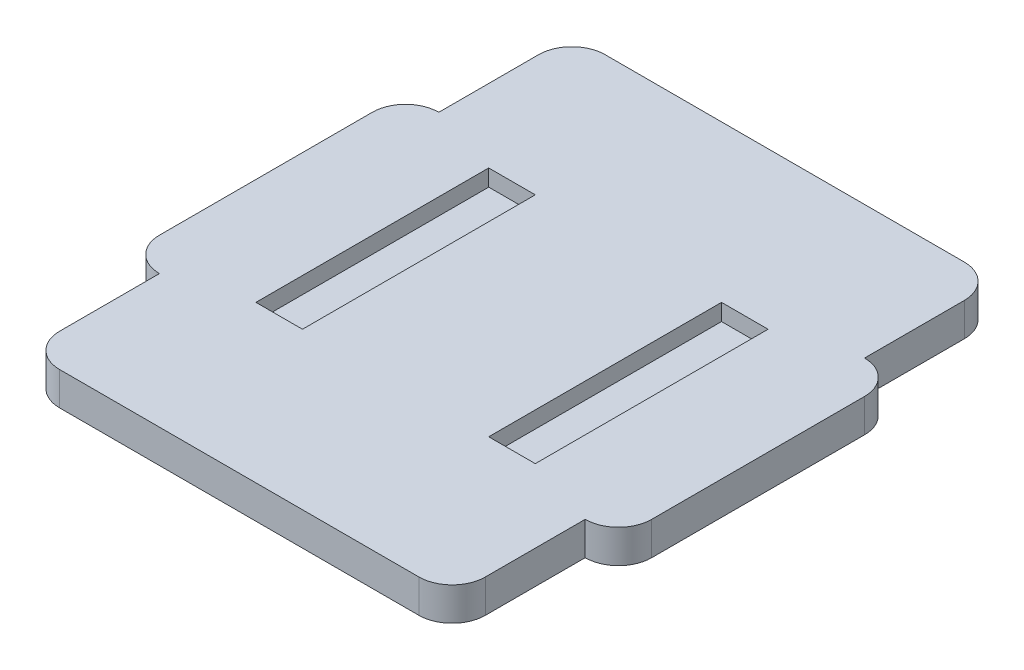
SolidWorks part; units mm, degrees
ref_plane "Front Plane" through (0, 0, 0) normal (0, 0, 1) x (1, 0, 0)
ref_plane "Top Plane" through (0, 0, 0) normal (0, 1, 0) x (1, 0, 0)
ref_plane "Right Plane" through (0, 0, 0) normal (1, 0, 0) x (0, 0, -1)
sketch "Sketch2" plane through (0, 0, 0) normal (0, 1, 0) x (1, 0, 0)
  line L0 (28, 21) -> (35, 21) construction
  line L1 (0, 0) -> (28, 0)
  line L2 (0, 0) -> (0, 42)
  line L3 (0, 42) -> (28, 42)
  line L4 (28, 0) -> (28, 42)
  line L5 (28, 42) -> (35, 42)
  line L6 (28, 42) -> (28, 0)
  line L7 (28, 0) -> (35, 0)
  line L8 (35, 42) -> (35, 0)
  line L9 (28, 38.5) -> (35, 38.5)
  line L10 (31.5, 38.5) -> (31.5, 3.5) construction
  line L11 (28, 3.5) -> (35, 3.5)
  line L12 (26, 0) -> (26, 42)
  line L13 (28, 42) -> (35, 42)
  line L14 (35, 42) -> (37, 42)
  line L15 (35, 42) -> (35, 0)
  line L16 (35, 0) -> (37, 0)
  line L17 (37, 42) -> (37, 0)
  line L18 (37, 42) -> (46, 42)
  line L19 (37, 42) -> (46, 42)
  line L22 (51, 37) -> (51, 5)
  line L23 (2, 42) -> (2, 0)
  line L24 (0, 38.5) -> (-7, 38.5)
  line L25 (0, 3.5) -> (-7, 3.5)
  line L26 (-7, 38.5) -> (-7, 3.5)
  line L27 (0, 42) -> (-7, 42)
  line L28 (-7, 42) -> (-7, 38.5)
  line L29 (0, 0) -> (-7, 0)
  line L30 (-7, 0) -> (-7, 3.5)
  line L31 (-7, 42) -> (-9, 42)
  line L32 (-9, 42) -> (-9, 0)
  line L33 (-9, 0) -> (-7, 0)
  line L34 (-9, 0) -> (-18, 0)
  line L35 (-23, 5) -> (-23, 37)
  line L36 (-18, 42) -> (-9, 42)
  line L37 (37, 0) -> (46, 0)
  line L39 (-18, 0) -> (46, 0)
  line L40 (-18, 0) -> (-18, -15)
  line L41 (-13, -20) -> (41, -20)
  line L42 (46, 0) -> (46, -15)
  line L43 (-18, 42) -> (46, 42)
  line L44 (-18, 42) -> (-18, 57)
  line L45 (-13, 62) -> (41, 62)
  line L46 (46, 42) -> (46, 57)
  arc A0 (51, 37) -> (46, 42) centre (46, 37) ccw
  arc A2 (-18, 0) -> (-23, 5) centre (-18, 5) cw
  arc A3 (-23, 37) -> (-18, 42) centre (-18, 37) cw
  arc A4 (46, 0) -> (51, 5) centre (46, 5) ccw
  arc A5 (-13, -20) -> (-18, -15) centre (-13, -15) cw
  arc A6 (41, -20) -> (46, -15) centre (41, -15) ccw
  arc A7 (46, 57) -> (41, 62) centre (41, 57) ccw
  arc A8 (-13, 62) -> (-18, 57) centre (-13, 57) ccw
  point P56 (46, -20)
  point P61 (-18, 62)
  dimension "D9" = 5
  dimension "D10" = 5
  dimension "D18" = 5
  dimension "D19" = 5
  dimension "D1" = 28
  dimension "D2" = 42
  dimension "D3" = 7
  dimension "D4" = 3.5
  dimension "D5" = 3.5
  dimension "D6" = 2
  dimension "D7" = 2
  dimension "D8" = 3.5
  dimension "D11" = 14
  dimension "D12" = 20
  dimension "D13" = 20
  dimension "D14" = 2
  dimension "D15" = 7
  dimension "D16" = 2
  dimension "D17" = 14
  dimension "D20" = 82
  dimension "D21" = 64
extrude "Boss-Extrude1" add sketch "Sketch2" along normal blind 5 contours L3 L23 L1 L12 | L12 L1 L4 L6 L3 | L11 L4 L7 L8 | L22 A0 L18 L17 | L17 L14 L8 L16 | L6 L9 L8 L5 | A3 L35 A2 L34 L32 L36 | L30 L29 L2 L25 | L32 L33 L30 L26 L28 L31 | L23 L3 L2 L1 | L27 L28 L24 L2 | L41 A6 L42 L37 L16 L7 L1 L29 L33 L34 L40 A5 | L45 A8 L44 L36 L31 L27 L3 L5 L14 L18 L46 A7 region at (1, 0, -21) region at (-3.5, 0, -1.75) region at (14, 0, 9.9249) region at (14, 0, -21) region at (-8, 0, -21) region at (27, 0, -21) region at (14, 0, -51.9249) region at (-3.5, 0, -40.25) region at (-15.8906, 0, -21) region at (31.5, 0, -1.75) region at (36, 0, -21) region at (31.5, 0, -40.25) region at (43.8906, 0, -21)
extrude "Boss-Extrude2" add sketch "Sketch2<3>" along normal blind 2.5 contours L24 L26 L25 L2 | L6 L11 L8 L9 region at (-3.5, 0, -21) region at (31.5, 0, -21)
sketch "Sketch2<3>" plane through (0, 0, 0) normal (0, 1, 0) x (1, 0, 0) same geometry as "Sketch2"
